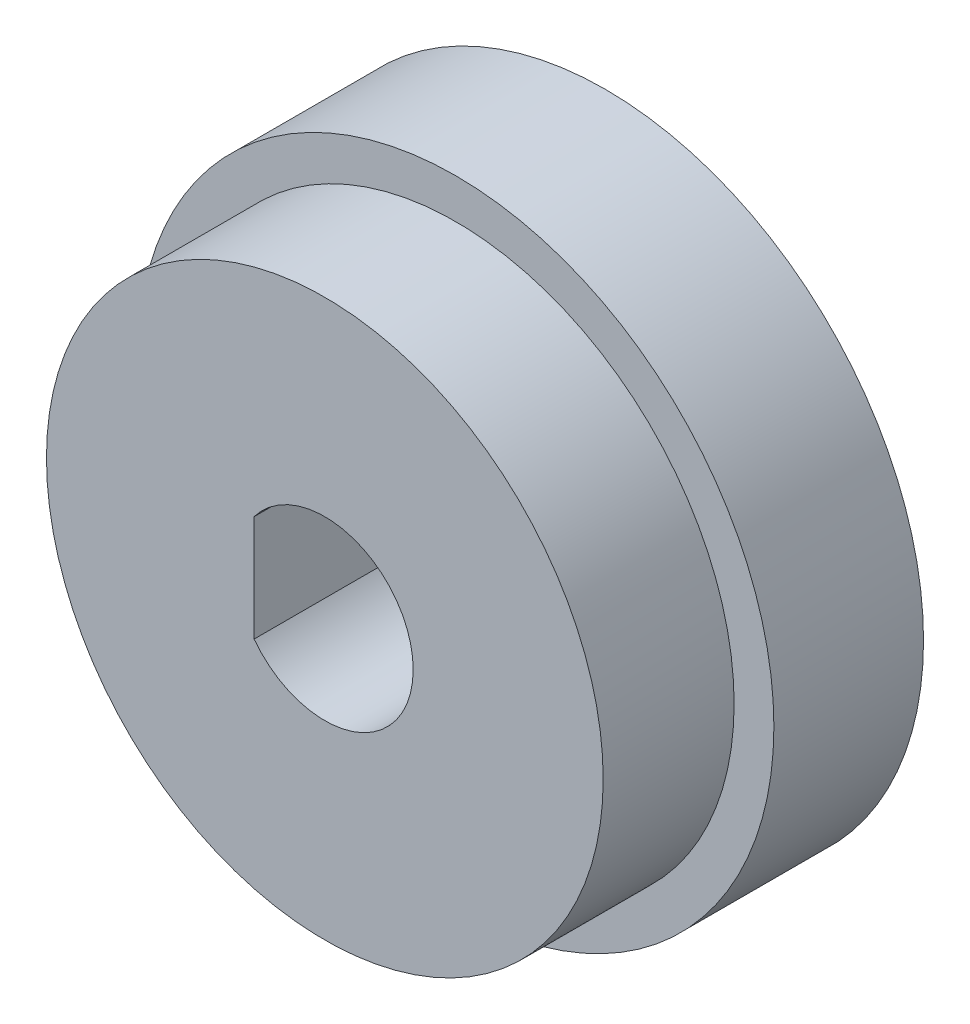
SolidWorks part; units mm, degrees
ref_plane "Front Plane" through (0, 0, 0) normal (0, 0, 1) x (1, 0, 0)
ref_plane "Top Plane" through (0, 0, 0) normal (0, 1, 0) x (1, 0, 0)
ref_plane "Right Plane" through (0, 0, 0) normal (1, 0, 0) x (0, 0, -1)
sketch "Sketch1" plane through (0, 0, 0) normal (0, 0, 1) x (1, 0, 0)
  circle A0 centre (0, 0) radius 10.8
  dimension "D1" = 21.6
extrude "Boss-Extrude1" add sketch "Sketch1" along normal blind 5.08
sketch "Sketch2" plane through (0, 0, 5.08) normal (0, 0, 1) x (1, 0, 0)
  circle A0 centre (0, 0) radius 9.45
  dimension "D1" = 18.9
extrude "Boss-Extrude2" add sketch "Sketch2" along normal blind 4.445
sketch "Sketch3" plane through (0, 0, 9.525) normal (0, 0, 1) x (1, 0, 0)
  line L3 (-2.4, 0) -> (-2.4, -1.8)
  line L4 (-2.4, 0) -> (-2.4, 1.8)
  arc A1 (-2.4, -1.8) -> (-2.4, 1.8) centre (0, 0) ccw
  dimension "D1" = 6
extrude "Cut-Extrude1" cut sketch "Sketch3" against normal through all
